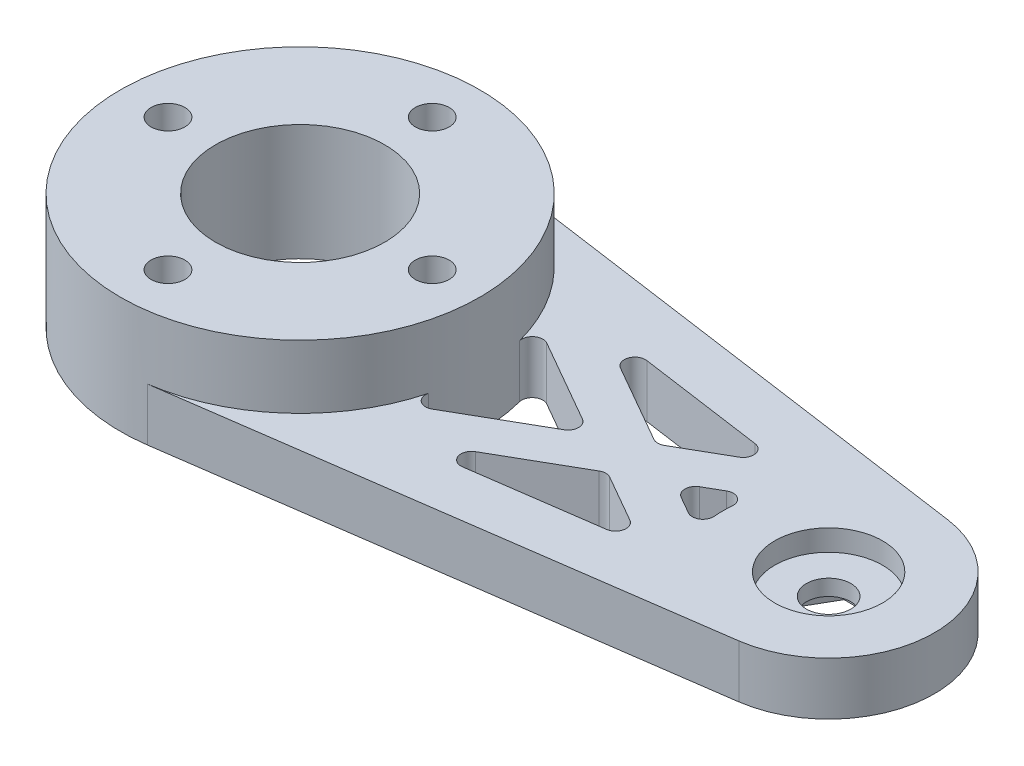
SolidWorks part; units mm, degrees
material "三聚氰胺甲醛树脂"
ref_plane "前视基准面" through (0, 0, 0) normal (0, 0, 1) x (1, 0, 0)
ref_plane "上视基准面" through (0, 0, 0) normal (0, 1, 0) x (1, 0, 0)
ref_plane "右视基准面" through (0, 0, 0) normal (1, 0, 0) x (0, 0, -1)
sketch "草图1" plane through (0, 0, 0) normal (0, 1, 0) x (1, 0, 0)
  line L0 (0, 0) -> (-5.9584, 0) construction
  line L1 (2.38, -16.8326) -> (51.4, -9.9015)
  line L2 (2.38, 16.8326) -> (51.4, 9.9015)
  line L3 (18.938, 9.4417) -> (38.9002, 6.6192)
  line L4 (18.938, -9.4417) -> (38.9002, -6.6192)
  line L5 (13.603, 10.196) -> (42.125, -6.1632) construction
  line L6 (13.603, -10.196) -> (42.125, 6.1632) construction
  line L7 (15.6062, 6.7414) -> (27.3598, 0)
  line L8 (18.938, 9.4417) -> (31.3796, 2.3056)
  line L9 (15.6062, -6.7414) -> (27.3598, 0)
  line L10 (18.938, -9.4417) -> (31.3796, -2.3056)
  line L11 (31.3796, 2.3056) -> (38.9002, 6.6192)
  line L12 (35.3994, 0) -> (40.4243, -2.8821)
  line L13 (35.3994, 0) -> (40.4243, 2.8821)
  line L14 (31.3796, -2.3056) -> (38.9002, -6.6192)
  line L16 (54.0415, 0) -> (52.0207, 3.5)
  line L17 (52.0207, 3.5) -> (47.9793, 3.5)
  line L18 (47.9793, 3.5) -> (45.9585, 0)
  line L19 (45.9585, 0) -> (47.9793, -3.5)
  line L20 (47.9793, -3.5) -> (52.0207, -3.5)
  line L21 (52.0207, -3.5) -> (54.0415, 0)
  circle A0 centre (0, 0) radius 12.5 construction
  circle A1 centre (-12.5, 0) radius 1.6
  circle A2 centre (0, 12.5) radius 1.6
  circle A3 centre (12.5, 0) radius 1.6
  circle A4 centre (0, -12.5) radius 1.6
  arc A5 (2.38, 16.8326) -> (2.38, -16.8326) centre (0, 0) ccw
  circle A6 centre (0, 0) radius 8
  arc A7 (40.4243, 2.8821) -> (40.4243, -2.8821) centre (50, 0) ccw
  circle A8 centre (50, 0) radius 2.1
  circle A9 centre (50, 0) radius 5.1
  arc A10 (15.6062, -6.7414) -> (15.6062, 6.7414) centre (0, 0) ccw
  circle A11 centre (0, 0) radius 17 construction
  arc A12 (51.4, -9.9015) -> (51.4, 9.9015) centre (50, 0) ccw
  circle A13 centre (50, 0) radius 10 construction
  circle A15 centre (50, 0) radius 4.0415 construction
  point P15 (0, 0)
  dimension "D1" = 25
  dimension "D2" = 3.2
  dimension "D4" = 20
  dimension "D5" = 34
  dimension "D6" = 16
  dimension "D7" = 4.2
  dimension "D8" = 10.2
  dimension "D15" = 7
  dimension "D3" = 50
  dimension "D9" = 5
  dimension "D10" = 5
  dimension "D11" = 2
  dimension "D12" = 2
  dimension "D13" = 2
  dimension "D14" = 2
extrude "凸台-拉伸1" add sketch "草图1" along normal blind 5 contours L1 A7 L2 A5 A9 A1 A2 A3 A4 A6 region at (-16.1583, 0, 0)
extrude "凸台-拉伸2" add sketch "草图1<3>" along normal blind 3 contours A9 A8 | A8 region at (52.9385, 0, 1.6965) region at (45.0442, 0, 0)
sketch "草图1<3>" plane through (0, 0, 0) normal (0, 1, 0) x (1, 0, 0) same geometry as "草图1"
fillet "圆角1" radius 1 3 edges at (35.3994, 2.5, 0) (40.4243, 2.5, -2.8821) (40.4243, 2.5, 2.8821)
fillet "圆角2" radius 1 3 edges at (31.3796, 2.5, 2.3056) (18.938, 2.5, 9.4417) (38.9002, 2.5, 6.6192)
fillet "圆角3" radius 1 3 edges at (18.938, 2.5, -9.4417) (31.3796, 2.5, -2.3056) (38.9002, 2.5, -6.6192)
fillet "圆角4" radius 1 3 edges at (15.6062, 2.5, -6.7414) (27.3598, 2.5, 0) (15.6062, 2.5, 6.7414)
sketch "草图2" plane through (0, 0, 0) normal (0, -1, 0) x (1, 0, 0)
  line L1 (53.9837, 0) -> (51.9919, 3.45)
  line L2 (51.9919, 3.45) -> (48.0081, 3.45)
  line L3 (48.0081, 3.45) -> (46.0163, 0)
  line L4 (46.0163, 0) -> (48.0081, -3.45)
  line L5 (48.0081, -3.45) -> (51.9919, -3.45)
  line L6 (51.9919, -3.45) -> (53.9837, 0)
  circle A0 centre (50, 0) radius 3.45 construction
  dimension "D1" = 6.9
extrude "切除-拉伸1" cut sketch "草图2" against normal blind 1.5
sketch "草图3" plane through (0, 5, 0) normal (0, 1, 0) x (1, 0, 0)
  circle A0 centre (0, 0) radius 17
  circle A1 centre (0, 0) radius 8 construction
  circle A2 centre (0, -12.5) radius 1.6 construction
  circle A3 centre (12.5, 0) radius 1.6 construction
  circle A4 centre (0, 12.5) radius 1.6 construction
  circle A5 centre (-12.5, 0) radius 1.6 construction
  circle A6 centre (0, 0) radius 8
  circle A7 centre (0, -12.5) radius 1.6
  circle A8 centre (12.5, 0) radius 1.6
  circle A9 centre (0, 12.5) radius 1.6
  circle A10 centre (-12.5, 0) radius 1.6
extrude "凸台-拉伸4" add sketch "草图3" along normal blind 6
